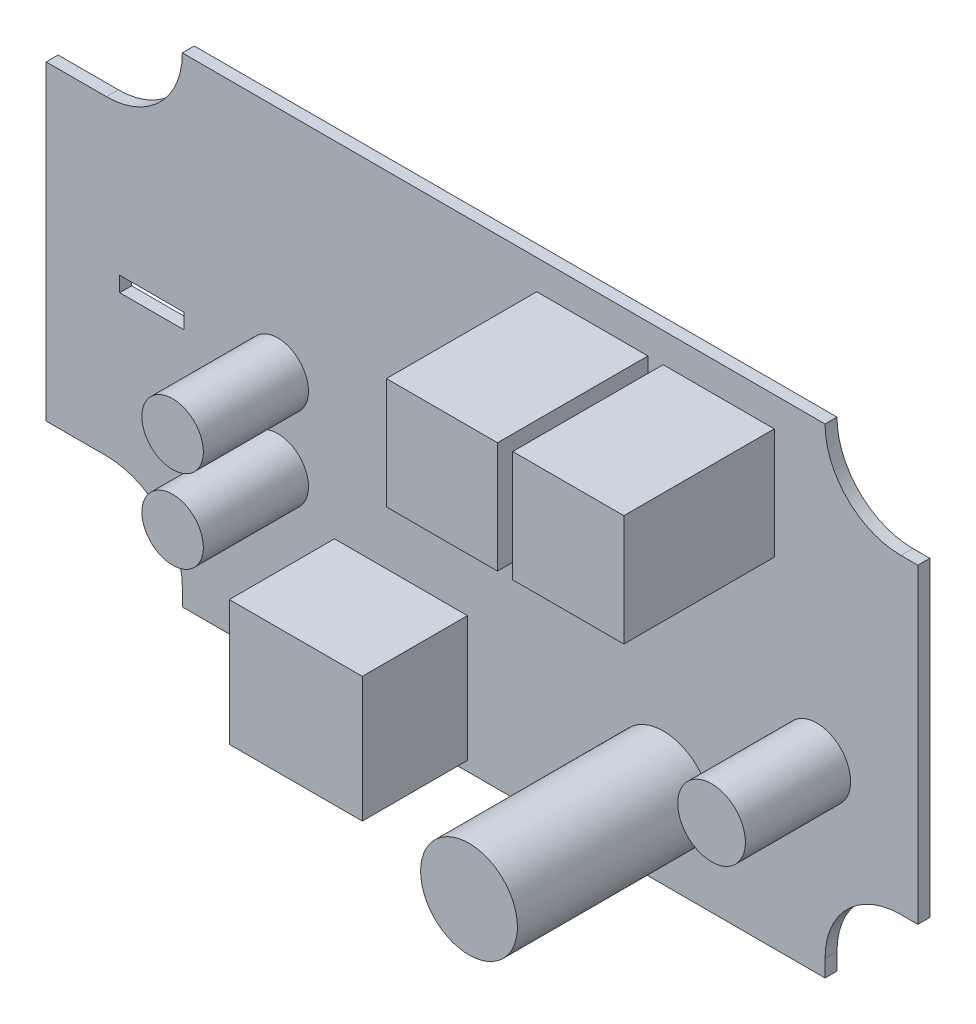
SolidWorks part; units mm, degrees
ref_plane "Front Plane" through (0, 0, 0) normal (0, 0, 1) x (1, 0, 0)
ref_plane "Top Plane" through (0, 0, 0) normal (0, 1, 0) x (1, 0, 0)
ref_plane "Right Plane" through (0, 0, 0) normal (1, 0, 0) x (0, 0, -1)
sketch "Sketch1" plane through (0, 0, 0) normal (0, 0, 1) x (1, 0, 0)
  line L0 (-42.3541, 30.2967) -> (-52.3541, 30.2967) construction
  line L1 (42.3541, -30.7033) -> (42.3541, -32.9433)
  line L2 (-52.3541, -20.7033) -> (-60.3013, -20.7033)
  line L3 (-42.3541, 30.2967) -> (42.3541, 30.2967)
  line L4 (52.3541, -20.7033) -> (54.5933, -20.7033)
  line L5 (-52.3541, 30.2967) -> (-52.3541, 20.2967) construction
  line L6 (-52.3541, -20.7033) -> (-52.3541, -30.7033) construction
  line L7 (-52.3541, -30.7033) -> (-42.3541, -30.7033) construction
  line L8 (42.3541, -30.7033) -> (52.3541, -30.7033) construction
  line L9 (52.3541, -30.7033) -> (52.3541, -20.7033) construction
  line L10 (52.3541, 20.2967) -> (52.3541, 30.2967) construction
  line L11 (52.3541, 30.2967) -> (42.3541, 30.2967) construction
  line L12 (54.5933, -20.7033) -> (54.5933, 20.2967)
  line L13 (-60.3013, -20.7033) -> (-60.3013, 20.2967)
  line L14 (-60.3013, 20.2967) -> (-52.3541, 20.2967)
  line L15 (54.5933, 20.2967) -> (52.3541, 20.2967)
  line L16 (42.3541, -32.9433) -> (-42.3541, -32.9433)
  line L17 (-42.3541, -32.9433) -> (-42.3541, -30.7033)
  line L18 (-50.6088, -0.2033) -> (-60.3013, -0.2033) construction
  line L19 (-42.1088, -1.2033) -> (-50.6088, -1.2033)
  line L20 (-42.1088, -1.2033) -> (-42.1088, 0.7967)
  line L21 (0, -32.9433) -> (0, 0) construction
  line L22 (-42.1088, 0.7967) -> (-50.6088, 0.7967)
  line L23 (-50.6088, -1.2033) -> (-50.6088, 0.7967)
  arc A0 (-42.3541, 30.2967) -> (-52.3541, 20.2967) centre (-52.3541, 30.2967) cw
  arc A2 (-52.3541, -20.7033) -> (-42.3541, -30.7033) centre (-52.3541, -30.7033) cw
  arc A4 (42.3541, 30.2967) -> (52.3541, 20.2967) centre (52.3541, 30.2967) ccw
  arc A5 (52.3541, -20.7033) -> (42.3541, -30.7033) centre (52.3541, -30.7033) ccw
  dimension "D1" = 41
  dimension "D2" = 2
  dimension "D3" = 10
  dimension "D4" = 8.5
  dimension "D5" = 84.7082
  dimension "D6" = 2.24
  dimension "D7" = 7.9472
  dimension "D8" = 2.2392
extrude "Boss-Extrude1" add sketch "Sketch1" along normal blind 1.5748
sketch "Sketch2" plane through (0, 0, 1.5748) normal (0, 0, 1) x (1, 0, 0)
  line L1 (4.3619, 26.3914) -> (19.0119, 26.3914)
  line L2 (4.3619, 26.3914) -> (4.3619, 11.7414)
  line L3 (4.3619, 11.7414) -> (19.0119, 11.7414)
  line L4 (19.0119, 26.3914) -> (19.0119, 11.7414)
  line L5 (21.0119, 26.3914) -> (35.6619, 26.3914)
  line L6 (21.0119, 26.3914) -> (21.0119, 11.7414)
  line L7 (21.0119, 11.7414) -> (35.6619, 11.7414)
  line L8 (35.6619, 26.3914) -> (35.6619, 11.7414)
  dimension "D1" = 2
  dimension "D2" = 14.65
extrude "Boss-Extrude2" add sketch "Sketch2" along normal blind 19.82
sketch "Sketch3" plane through (0, 0, 1.5748) normal (0, 0, 1) x (1, 0, 0)
  circle A0 centre (21.0509, -21.7791) radius 6.38
  dimension "D1" = 12.76
extrude "Boss-Extrude3" add sketch "Sketch3" along normal blind 25.62
sketch "Sketch4" plane through (0, 0, 1.5748) normal (0, 0, 1) x (1, 0, 0)
  line L1 (-22.3027, -15.1438) -> (-4.7739, -15.1438)
  line L2 (-22.3027, -15.1438) -> (-22.3027, -31.671)
  line L3 (-22.3027, -31.671) -> (-4.7739, -31.671)
  line L4 (-4.7739, -15.1438) -> (-4.7739, -31.671)
  circle A0 centre (-29.7754, 0) radius 4.05
  circle A1 centre (-29.7754, -10.91) radius 4.05
  circle A2 centre (41.2613, -8.8411) radius 4.4585
  dimension "D1" = 8.1
  dimension "D2" = 16.5272
  dimension "D4" = 8.9169
  dimension "D3" = 17.5288
extrude "Boss-Extrude4" add sketch "Sketch4" along normal blind 13.86
